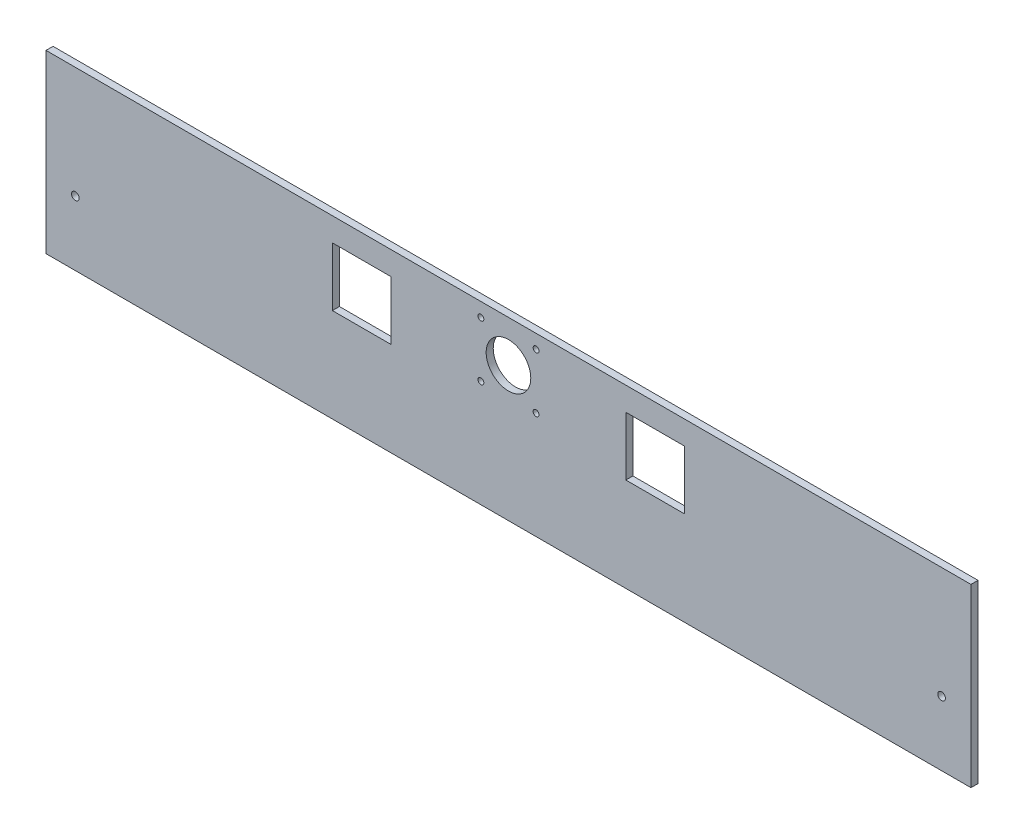
SolidWorks part; units mm, degrees
note: The reader was unsure of these and kept them because the rebuilt part matched: thickness of "Base-Flange1", "Sheet-Metal1", "Sheet-Metal2", "Sheet-Metal3", "Sheet-Metal4".
ref_plane "Front Plane" through (0, 0, 0) normal (0, 0, 1) x (1, 0, 0)
ref_plane "Top Plane" through (0, 0, 0) normal (0, 1, 0) x (1, 0, 0)
ref_plane "Right Plane" through (0, 0, 0) normal (1, 0, 0) x (0, 0, -1)
sketch "Sketch1" plane through (0, 0, 0) normal (0, 0, 1) x (1, 0, 0)
  line L1 (-394, -75) -> (394, -75)
  line L2 (-394, -75) -> (-394, 75)
  line L3 (-394, 75) -> (394, 75)
  line L4 (394, -75) -> (394, 75)
  line L5 (-394, -75) -> (394, 75) construction
  line L6 (-394, 75) -> (394, -75) construction
  point P0 (0, 0)
  dimension "D1" = 150
  dimension "D2" = 788
base flange "Base-Flange1" sketch "Sketch1" thickness 6 reverse thickness direction no parameters "D1"=2
sketch "Sketch2" plane through (0, 0, 0) normal (0, 0, 1) x (1, 0, 0)
  line L0 (-125, 30) -> (125, 30) construction
  line L1 (-150, 5) -> (-100, 5)
  line L2 (-150, 5) -> (-150, 55)
  line L3 (-150, 55) -> (-100, 55)
  line L4 (-100, 5) -> (-100, 55)
  line L5 (-150, 5) -> (-100, 55) construction
  line L6 (-150, 55) -> (-100, 5) construction
  line L7 (100, 5) -> (150, 5)
  line L8 (100, 5) -> (100, 55)
  line L9 (100, 55) -> (150, 55)
  line L10 (150, 5) -> (150, 55)
  line L11 (100, 5) -> (150, 55) construction
  line L12 (100, 55) -> (150, 5) construction
  line L13 (0, 30) -> (0, 0) construction
  line L15 (394, 75) -> (-394, 75) construction
  point P0 (-125, 30)
  point P5 (125, 30)
  dimension "D1" = 70
  dimension "D2" = 200
  dimension "D3" = 50
extrude "Cut-Extrude1" cut sketch "Sketch2" against normal through all
sketch "Sketch3" plane through (0, 0, 0) normal (0, 0, 1) x (1, 0, 0)
  line L0 (0, 0) -> (0, 39.65) construction
  line L1 (-23.5, 16.15) -> (23.5, 16.15) construction
  line L2 (-23.5, 16.15) -> (-23.5, 63.15) construction
  line L3 (-23.5, 63.15) -> (23.5, 63.15) construction
  line L4 (23.5, 16.15) -> (23.5, 63.15) construction
  line L5 (-23.5, 16.15) -> (23.5, 63.15) construction
  line L6 (-23.5, 63.15) -> (23.5, 16.15) construction
  line L7 (394, 75) -> (-394, 75) construction
  circle A0 centre (0, 39.65) radius 19
  circle A1 centre (23.5, 63.15) radius 2.5
  circle A2 centre (23.5, 16.15) radius 2.5
  circle A3 centre (-23.5, 16.15) radius 2.5
  circle A4 centre (-23.5, 63.15) radius 2.5
  dimension "D2" = 38
  dimension "D4" = 5
  dimension "D1" = 47
  dimension "D3" = 35.35
extrude "Cut-Extrude2" cut sketch "Sketch3" against normal blind 10
sketch "Sketch4" plane through (0, 0, 0) normal (0, 0, 1) x (1, 0, 0)
  line L0 (-369, -20) -> (369, -20) construction
  line L1 (0, 0) -> (0, -20) construction
  line L2 (394, 75) -> (-394, 75) construction
  line L3 (394, -75) -> (394, 75) construction
  circle A0 centre (369, -20) radius 3.25
  circle A1 centre (-369, -20) radius 3.25
  point P3 (0, -20)
  dimension "D3" = 6.5
  dimension "D1" = 95
  dimension "D2" = 25
extrude "Cut-Extrude3" cut sketch "Sketch4" against normal blind 10
sketch "Bend-Lines1" [suppressed] plane through (0, 0, 0) normal (0, 1, 0) x (1, 0, 0)
sketch "Bounding-Box1" [suppressed] plane through (0, 0, 0) normal (0, 1, 0) x (1, 0, 0)
sheet metal parameters "Sheet-Metal1" thickness 6 parameters "D1"=2, "D7"=1.5
flat pattern "Flat-Pattern1" [suppressed]
sketch "Bend-Lines2" plane through (0, 0, 0) normal (0, 1, 0) x (1, 0, 0)
sketch3d "Bounding-Box2" [suppressed]
  line L0 (-400, -75, 0) -> (400, -75, 0) construction
  line L1 (-400, 75, 0) -> (400, 75, 0) construction
  line L2 (-400, -75, 0) -> (-400, 75, 0) construction
  line L3 (400, -75, 0) -> (400, 75, 0) construction
sheet metal parameters "Sheet-Metal2" thickness 6 parameters "D1"=2, "D7"=1.5
flat pattern "Flat-Pattern1"
sketch "Bend-Lines2" plane through (0, 0, 0) normal (0, 1, 0) x (1, 0, 0)
sketch3d "Bounding-Box2" [suppressed]
  line L0 (-394, -75, 0) -> (394, -75, 0) construction
  line L1 (-394, 75, 0) -> (394, 75, 0) construction
  line L2 (-394, -75, 0) -> (-394, 75, 0) construction
  line L3 (394, -75, 0) -> (394, 75, 0) construction
sheet metal parameters "Sheet-Metal3" thickness 6 parameters "D1"=2, "D7"=1.5
flat pattern "Flat-Pattern1"
sketch "Bend-Lines2" plane through (0, 0, 0) normal (0, 1, 0) x (1, 0, 0)
sketch3d "Bounding-Box2" [suppressed]
  line L0 (-394, -75, 0) -> (394, -75, 0) construction
  line L1 (-394, 75, 0) -> (394, 75, 0) construction
  line L2 (-394, -75, 0) -> (-394, 75, 0) construction
  line L3 (394, -75, 0) -> (394, 75, 0) construction
sheet metal parameters "Sheet-Metal4" thickness 6 parameters "D1"=2, "D7"=1.5
flat pattern "Flat-Pattern1"
sketch "Bend-Lines2" plane through (0, 0, 0) normal (0, 1, 0) x (1, 0, 0)
sketch3d "Bounding-Box2" [suppressed]
  line L0 (-394, -75, 0) -> (394, -75, 0) construction
  line L1 (-394, 75, 0) -> (394, 75, 0) construction
  line L2 (-394, -75, 0) -> (-394, 75, 0) construction
  line L3 (394, -75, 0) -> (394, 75, 0) construction
